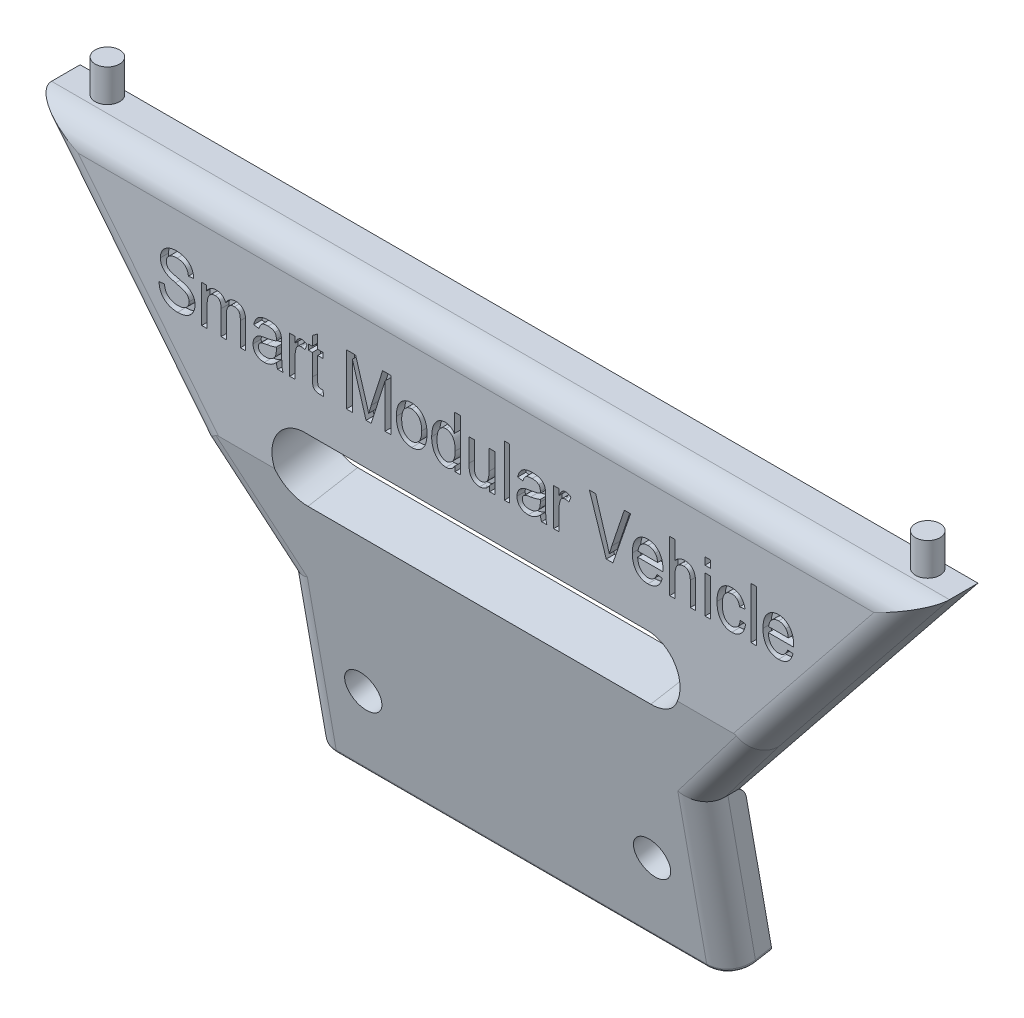
SolidWorks part; units mm, degrees
ref_plane "Front Plane" through (0, 0, 0) normal (0, 0, 1) x (1, 0, 0)
ref_plane "Top Plane" through (0, 0, 0) normal (0, 1, 0) x (1, 0, 0)
ref_plane "Right Plane" through (0, 0, 0) normal (1, 0, 0) x (0, 0, -1)
sketch "Sketch1" plane through (0, 0, 0) normal (0, 0, 1) x (1, 0, 0)
  line L0 (-55, 0) -> (55, 0)
  line L1 (55, 0) -> (25.6917, -36.5)
  line L2 (25.6917, -36.5) -> (25.6917, -56.5)
  line L3 (25.6917, -56.5) -> (-25.6917, -56.5)
  line L4 (0, -56.5) -> (0, 0) construction
  line L9 (-25.6917, -36.5) -> (-25.6917, -56.5)
  line L10 (-55, 0) -> (-25.6917, -36.5)
extrude "Boss-Extrude1" add sketch "Sketch1" against normal blind 6.5
sketch "Sketch2" plane through (25.6917, 0, 0) normal (1, 0, 0) x (0, 0, -1)
  line L3 (7.2, -36.5) -> (6.5, -36.5)
  line L4 (6.5, -36.5) -> (6.5, -56.5)
  line L5 (6.5, -56.5) -> (10.5897, -55.781)
  line L6 (12.65, -67.5) -> (7.6125, -38.8463) construction
  line L7 (10.5897, -55.781) -> (7.2, -36.5)
  point P0 (0, 0)
extrude "Boss-Extrude2" add sketch "Sketch2" against normal up to surface (51.3835 mm away) up to face at (-25.6917, -46.5, -3.25)
sketch "Sketch3" plane through (25.6917, 0, 0) normal (1, 0, 0) x (0, 0, -1)
  line L0 (2.1233, -36.5) -> (5.6394, -56.5)
  line L1 (10.5897, -55.781) -> (7.2, -36.5) construction
  line L3 (6.5, -36.5) -> (0, -36.5) construction
  line L6 (2.1233, -36.5) -> (0, -24.4224)
  line L7 (0, -36.5) -> (0, 0) construction
  line L8 (0, -24.4224) -> (0, -56.5)
  line L9 (0, -56.5) -> (5.6394, -56.5)
  line L10 (6.5, -56.5) -> (0, -56.5) construction
  dimension "D1" = 5
sketch "Sketch4" plane through (0, 0, 0) normal (0, 1, 0) x (1, 0, 0)
  circle A0 centre (-50.1569, 5) radius 1.5
  circle A1 centre (50.3431, 5) radius 1.5
  dimension "D1" = 3
  dimension "D2" = 3
extrude "Boss-Extrude3" add sketch "Sketch4" along normal blind 4
fillet "Fillet1" radius 2 1 edges at (0, -36.5, -7.2)
extrude "Cut-Extrude3" cut sketch "Sketch3" against normal through all both and the other way through all
sketch "Sketch6" plane through (0, -0.7322, 4.1649) normal (0, -0.1732, 0.9849) x (1, 0, 0)
  line L0 (-25.6917, -46.4697) -> (25.6917, -46.4697) construction
  line L1 (-25.6917, -36.3163) -> (-25.6917, -56.6231) construction
  line L2 (25.6917, -56.6231) -> (25.6917, -36.3163) construction
  circle A0 centre (-17.6917, -46.4697) radius 2.25
  circle A1 centre (17.6917, -46.4697) radius 2.25
  dimension "D3" = 4.5
  dimension "D4" = 4.5
  dimension "D1" = 8
  dimension "D2" = 8
extrude "Cut-Extrude4" cut sketch "Sketch6" against normal through all
fillet "Fillet2" radius 3 8 edges at (30.5407, -30.4612, -1.0617) (-30.5407, -30.4612, -1.0617) (-25.6917, -46.5, -3.8814) (-45.1948, -12.2112, 0) (25.6917, -46.5, -3.8814) (45.1948, -12.2112, 0) (0, 0, 0) (0, -56.5, -6.5)
sketch "Sketch7" plane through (0, 0, 0) normal (0, 0, 1) x (1, 0, 0)
  line L0 (-40.1429, -13.7112) -> (40.1429, -13.7112) construction
  line L1 (-48.7437, -3) -> (-31.5422, -24.4224) construction
  line L2 (31.5422, -24.4224) -> (48.7437, -3) construction
  text T0 "Smart Modular Vehicle" font "Arial Narrow" height in points 24
extrude "Cut-Extrude5" cut sketch "Sketch7" against normal blind 1
sketch "Sketch8" plane through (0, -0.7322, 4.1649) normal (0, -0.1732, 0.9849) x (1, 0, 0)
  line L0 (-21, -22.4741) -> (21, -22.4741) construction
  line L1 (-21, -18.4741) -> (21, -18.4741)
  line L2 (-21, -26.4741) -> (21, -26.4741)
  line L3 (54.9055, -0.4741) -> (-54.9055, -0.4741) construction
  line L5 (0, 0) -> (0, -56.6231) construction
  line L6 (-22.6917, -56.6231) -> (22.6917, -56.6231) construction
  arc A2 (-21, -18.4741) -> (-21, -26.4741) centre (-21, -22.4741) ccw
  arc A3 (21, -26.4741) -> (21, -18.4741) centre (21, -22.4741) ccw
  point P2 (0, -22.4741)
  dimension "D1" = 42
  dimension "D2" = 8
  dimension "D3" = 22
extrude "Cut-Extrude6" cut sketch "Sketch8" against normal through all
fillet "Fillet5" radius 0.5 9 edges at (-25.6917, -55.9542, -9.6048) (-25.5191, -56.301, -7.632) (-23.6323, -56.5, -5.793) (25.6917, -55.9542, -9.6048) (25.5191, -56.301, -7.632) (23.6323, -56.5, -5.793) (0, -56.5, -5.6394)
